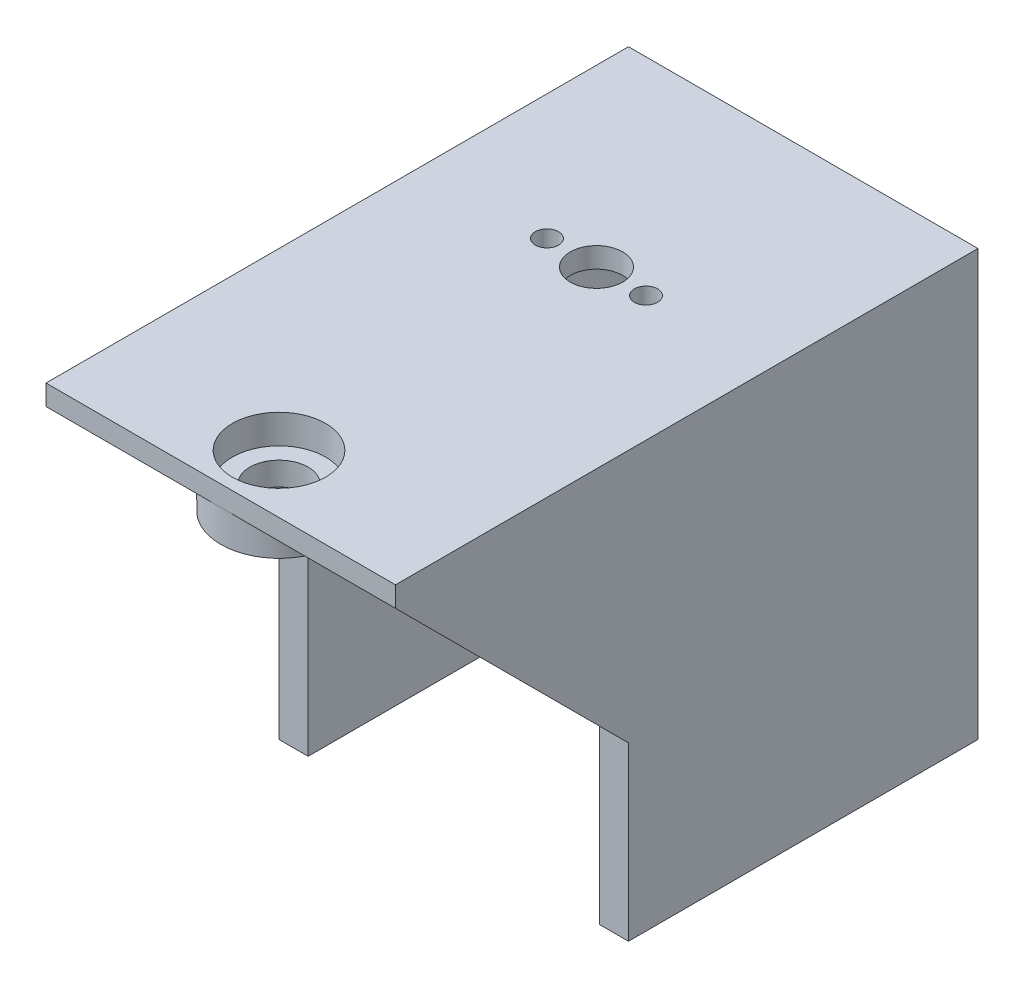
SolidWorks part; units mm, degrees
ref_plane "Alzado" through (0, 0, 0) normal (0, 0, 1) x (1, 0, 0)
ref_plane "Planta" through (0, 0, 0) normal (0, 1, 0) x (1, 0, 0)
ref_plane "Vista lateral" through (0, 0, 0) normal (1, 0, 0) x (0, 0, -1)
sketch "Croquis1" plane through (0, 0, 0) normal (0, 1, 0) x (1, 0, 0)
  line L1 (-30, -30) -> (30, -30)
  line L2 (-30, -30) -> (-30, 30)
  line L3 (-30, 30) -> (30, 30)
  line L4 (30, -30) -> (30, 30)
  line L5 (-30, -30) -> (30, 30) construction
  line L6 (-30, 30) -> (30, -30) construction
  point P0 (0, 0)
  dimension "D1" = 60
  dimension "D2" = 60
extrude "Saliente-Extruir1" add sketch "Croquis1" along normal blind 73
sketch "Croquis2" plane through (0, 0, 30) normal (0, 0, 1) x (1, 0, 0)
  line L0 (-30, 0) -> (30, 0) construction
  line L1 (-25, 0) -> (25, 0)
  line L2 (-25, 0) -> (-25, 69.5)
  line L3 (-25, 69.5) -> (25, 69.5)
  line L4 (25, 0) -> (25, 69.5)
  line L5 (-30, 73) -> (-30, 0) construction
  line L8 (-30, 73) -> (30, 73) construction
  dimension "D1" = 50
  dimension "D2" = 5
  dimension "D3" = 3.5
extrude "Cortar-Extruir1" cut sketch "Croquis2" against normal up to next
sketch "Croquis3" plane through (0, 73, 0) normal (0, 1, 0) x (1, 0, 0)
  line L0 (-8.5, -5.5) -> (-6.5, -5.5)
  line L3 (6.5, -5.5) -> (8.5, -5.5)
  line L4 (30, 30) -> (-30, 30) construction
  circle A1 centre (-8.5, -5.5) radius 2
  circle A2 centre (8.5, -5.5) radius 2
  point P6 (0, 0)
  dimension "D1" = 35.5
  dimension "D3" = 4
  dimension "D4" = 4
  dimension "D2" = 17
extrude "Cortar-Extruir2" cut sketch "Croquis3" against normal up to next contours A2 | A1 region at (-10.4434, 73, 5.5) region at (8.5, 73, 7.4434)
chamfer "Chaflán1" distance 5 angle 45 2 edges at (25, 69.5, 0) (-25, 69.5, 0)
sketch "Croquis5" plane through (0, 0, 0) normal (0, -1, 0) x (1, 0, 0)
  line L0 (30, -30) -> (25, -30) construction
  line L2 (30, 30) -> (30, -30) construction
  circle A0 centre (27.5, -20) radius 1.6021
  circle A1 centre (27.5, 20) radius 1.1306
  point P0 (27.5, -20)
  point P2 (27.5, 20)
  dimension "D2" = 10
  dimension "D3" = 2.5
  dimension "D1" = 40
hole_wizard "Taladro de margen para M31" positions "Croquis5" profile "Croquis6" hole size "M3" standard "GB"
sketch "Croquis6" plane through (27.5, 0, -20) normal (1, 0, 0) x (0, 0, -1)
  line L0 (0, 0) -> (0, 41.0215)
  line L1 (0, 41.0215) -> (1.7, 40)
  line L2 (1.7, 40) -> (1.7, 0)
  line L5 (1.7, 0) -> (0, 0)
  line L10 (0, 41.0215) -> (-1.7, 40) construction
  line L11 (0, -6.35) -> (0, 107.95) construction
  dimension "Di醡etro de taladro" = 3.4
  dimension "Profundidad de taladro" = 40
  dimension "羘gulo de perforador" = 118
sketch "Croquis7" plane through (0, 0, 0) normal (0, -1, 0) x (1, 0, 0)
  line L0 (-30, -30) -> (-30, 30) construction
  circle A0 centre (-27.5, 20) radius 1.3907
  circle A1 centre (-27.5, -20) radius 1.8898
  point P0 (-27.5, 20)
  point P2 (-27.5, -20)
  dimension "D1" = 2.5
  dimension "D2" = 2.5
hole_wizard "Taladro de margen para M32" positions "Croquis7" profile "Croquis8" hole size "M3" standard "GB"
sketch "Croquis8" plane through (-27.5, 0, 20) normal (1, 0, 0) x (0, 0, -1)
  line L0 (0, 0) -> (0, 41.0215)
  line L1 (0, 41.0215) -> (1.7, 40)
  line L2 (1.7, 40) -> (1.7, 0)
  line L5 (1.7, 0) -> (0, 0)
  line L10 (0, 41.0215) -> (-1.7, 40) construction
  line L11 (0, -6.35) -> (0, 107.95) construction
  dimension "Di醡etro de taladro" = 3.4
  dimension "Profundidad de taladro" = 40
  dimension "羘gulo de perforador" = 118
sketch "Croquis9" plane through (0, 0, 0) normal (0, -1, 0) x (1, 0, 0)
  circle A0 centre (-27.5, 0) radius 1.7835
  circle A1 centre (27.5, 1.7835) radius 1.8209
  point P0 (-27.5, 0)
  point P2 (27.5, 1.7835)
hole_wizard "Taladro de margen para M33" positions "Croquis9" profile "Croquis10" hole size "M3" standard "GB"
sketch "Croquis10" plane through (-27.5, 0, 0) normal (1, 0, 0) x (0, 0, -1)
  line L0 (0, 0) -> (0, 41.0215)
  line L1 (0, 41.0215) -> (1.7, 40)
  line L2 (1.7, 40) -> (1.7, 0)
  line L5 (1.7, 0) -> (0, 0)
  line L10 (0, 41.0215) -> (-1.7, 40) construction
  line L11 (0, -6.35) -> (0, 107.95) construction
  dimension "Di醡etro de taladro" = 3.4
  dimension "Profundidad de taladro" = 40
  dimension "羘gulo de perforador" = 118
sketch "Croquis11" plane through (0, 0, 30) normal (0, 0, 1) x (1, 0, 0)
  line L0 (30, 73) -> (30, 0) construction
  line L1 (-30, 73) -> (30, 73)
  line L2 (-30, 73) -> (-30, 69.5)
  line L3 (-30, 69.5) -> (30, 69.5)
  line L4 (30, 73) -> (30, 69.5)
extrude "Saliente-Extruir2" add sketch "Croquis11" along normal blind 40
chamfer "Chaflán2" distance 40 angle 45 2 edges at (25, 69.5, 30) (-25, 69.5, 30)
sketch "Croquis12" plane through (0, 73, 0) normal (0, 1, 0) x (1, 0, 0)
  line L2 (30, 30) -> (-30, 30) construction
  circle A0 centre (0, -60) radius 2.5
  dimension "D2" = 5
  dimension "D1" = 90
extrude "Cortar-Extruir3" cut sketch "Croquis12" against normal up to next contours A0 region at (0, 73, 60)
sketch "Croquis13" plane through (0, 73, 0) normal (0, 1, 0) x (1, 0, 0)
  circle A0 centre (0, -60) radius 8
  dimension "D1" = 16
sketch "Croquis14" plane through (0, 73, 0) normal (0, 1, 0) x (1, 0, 0)
  circle A0 centre (0, -60) radius 10
  circle A1 centre (0, -60) radius 8
  dimension "D1" = 20
  dimension "D2" = 16
extrude "Saliente-Extruir3" add sketch "Croquis14" against normal blind 7 contours A0
sketch "Croquis15" plane through (0, 66, 0) normal (0, -1, 0) x (1, 0, 0)
  circle A3 centre (0, 60) radius 10
  dimension "D1" = 20
extrude "Saliente-Extruir4" add sketch "Croquis15" along normal blind 2
extrude "Cortar-Extruir5" cut sketch "Croquis13" against normal blind 5
sketch "Croquis16" plane through (0, 68, 0) normal (0, 1, 0) x (1, 0, 0)
  circle A0 centre (0, -60) radius 5
  dimension "D1" = 10
extrude "Cortar-Extruir6" cut sketch "Croquis16" against normal blind 5
sketch "Croquis17" plane through (0, 73, 0) normal (0, 1, 0) x (1, 0, 0)
  circle A0 centre (0, -5.5) radius 4.5
  circle A1 centre (0, -60) radius 5 construction
  dimension "D1" = 54.5
  dimension "D2" = 9
extrude "Cortar-Extruir7" cut sketch "Croquis17" against normal blind 16
